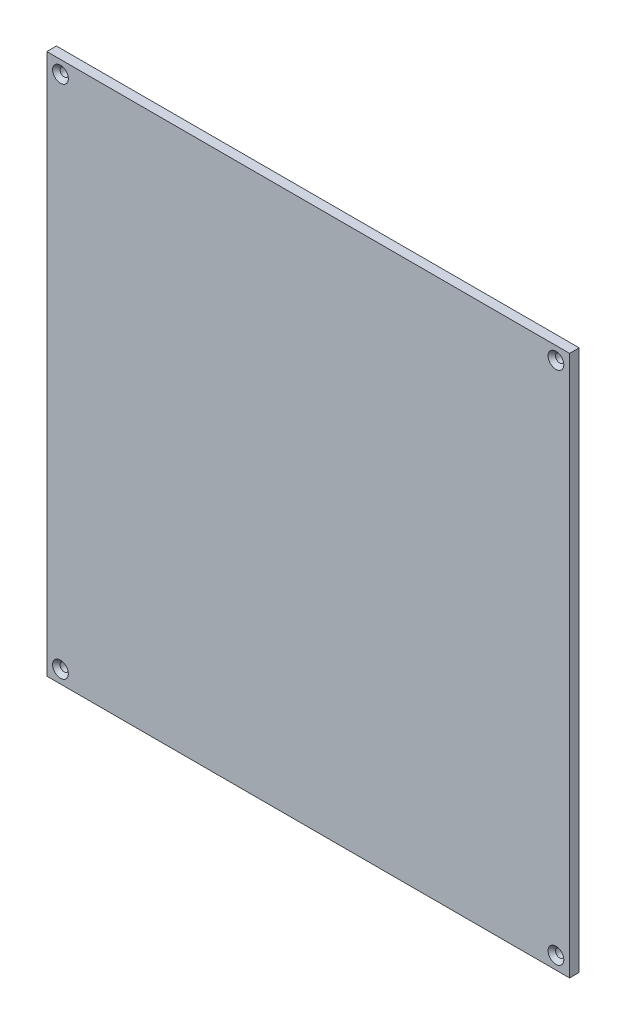
SolidWorks part; units mm, degrees
ref_plane "Front Plane" through (0, 0, 0) normal (0, 0, 1) x (1, 0, 0)
ref_plane "Top Plane" through (0, 0, 0) normal (0, 1, 0) x (1, 0, 0)
ref_plane "Right Plane" through (0, 0, 0) normal (1, 0, 0) x (0, 0, -1)
sketch "Model" plane through (0, 0, 0) normal (0, 0, 1) x (1, 0, 0)
  line L0 (-173, 179) -> (173, 179)
  line L1 (-173, -179) -> (173, -179)
  line L7 (-173, -179) -> (-173, 179)
  line L14 (173, 0) -> (-173, 0) construction
  line L18 (0, 179) -> (0, -179) construction
  line L23 (173, 179) -> (173, -179)
  point P1 (0, 0)
  dimension "D1" = 358
  dimension "D2" = 346
extrude "Boss-Extrude1" add sketch "Model" along normal blind 6.35 contours L23 L7 region at (0, 0, 0)
sketch "Sketch2" plane through (0, 0, 6.35) normal (0, 0, 1) x (1, 0, 0)
  line L0 (173, 0) -> (-173, 0) construction
  line L1 (173, 179) -> (173, -179) construction
  line L2 (-173, -179) -> (-173, 179) construction
  line L3 (0, 179) -> (0, -179) construction
  line L6 (-173, 179) -> (173, 179) construction
  line L7 (-173, -179) -> (173, -179) construction
  circle A0 centre (-163.95, 170.5) radius 2.55
  circle A1 centre (163.95, 170.5) radius 2.55
  circle A2 centre (163.95, -170.5) radius 2.55
  circle A3 centre (-163.95, -170.5) radius 2.55
  dimension "D1" = 5.1
  dimension "D3" = 341
  dimension "D2" = 327.9
extrude "Cut-Extrude1" cut sketch "Sketch2" against normal up to next contours A0 | A3 | A2 | A1 region at (-163.95, 170.5, 6.35) region at (163.95, 170.5, 6.35) region at (163.95, -170.5, 6.35) region at (-163.95, -170.5, 6.35)
hole_wizard "CSK for M5 Flat Head Machine Screw1" positions "Sketch3" profile "Sketch4" countersink size "M5" standard "ANSI Metric" end condition through all
sketch "Sketch3" plane through (0, 0, 6.35) normal (0, 0, 1) x (1, 0, 0)
  point P0 (-163.95, 170.5)
  point P3 (163.95, 170.5)
  point P6 (163.95, -170.5)
  point P9 (-163.95, -170.5)
sketch "Sketch4" plane through (-163.95, 170.5, 6.35) normal (1, 0, 0) x (0, -1, 0)
  line L0 (0, 0) -> (0, 6.35)
  line L1 (0, 6.35) -> (2.75, 6.35)
  line L2 (2.75, 6.35) -> (2.75, 2.45)
  line L3 (2.75, 2.45) -> (5.2, 0)
  line L5 (5.2, 0) -> (0, 0)
  line L6 (-2.75, 2.45) -> (-5.2, 0) construction
  line L11 (0, -6.35) -> (0, 107.95) construction
  dimension "Thru Hole Dia." = 5.5
  dimension "Thru Hole Depth" = 6.35
  dimension "Near C'Sink Dia." = 10.4
  dimension "Near C'Sink Angle" = 90
sketch "Sketch5" plane through (0, 0, 0) normal (0, 0, -1) x (-1, 0, 0)
  line L0 (0, 0) -> (-2.1213, 2.1213) construction
  line L1 (-7.5, -7.5) -> (7.5, -7.5) construction
  line L2 (-7.5, -7.5) -> (-7.5, 7.5) construction
  line L3 (-7.5, 7.5) -> (7.5, 7.5) construction
  line L4 (7.5, -7.5) -> (7.5, 7.5) construction
  line L5 (-7.5, -7.5) -> (7.5, 7.5) construction
  line L6 (-7.5, 7.5) -> (7.5, -7.5) construction
  circle A2 centre (0, 0) radius 1.5 construction
  circle A3 centre (-2.1213, 2.1213) radius 0.75
  point P0 (0, 0)
  point P10 (-2.321, 2.321)
  dimension "D3" = 3
  dimension "D4" = 1.5
  dimension "D5" = 3
  dimension "D1" = 15
  dimension "D2" = 15
extrude "Cut-Extrude2" cut sketch "Sketch5" against normal offset from surface (4.35 mm away) 2 up to face at (-158.75, 170.5, 6.35)
hole_wizard "M3x0.5 Tapped Hole1" positions "3DSketch1" profile "Sketch6" tap size "M3x0.5" standard "ANSI Metric"
sketch3d "3DSketch1"
  point P0 (0, 0, 0)
sketch "Sketch6" plane through (0, 0, 0) normal (1, 0, 0) x (0, 1, 0)
  line L0 (0, 0) -> (0, 5.7511)
  line L1 (0, 5.7511) -> (1.25, 5)
  line L2 (1.25, 5) -> (1.25, 0.275)
  line L3 (1.25, 0.275) -> (1.525, 0)
  line L5 (1.525, 0) -> (0, 0)
  line L6 (-1.25, 0.275) -> (-1.525, 0) construction
  line L10 (0, 5.7511) -> (-1.25, 5) construction
  line L11 (0, -6.35) -> (0, 107.95) construction
  dimension "Tap Drill Dia." = 2.5
  dimension "Tap Drill Depth" = 5
  dimension "Near C'Sink Dia." = 3.05
  dimension "Near C'Sink Angle" = 90
  dimension "Drill Angle" = 118
cosmetic thread "Hole Thread1" parameters "D1"=4.5, "D2"=3
